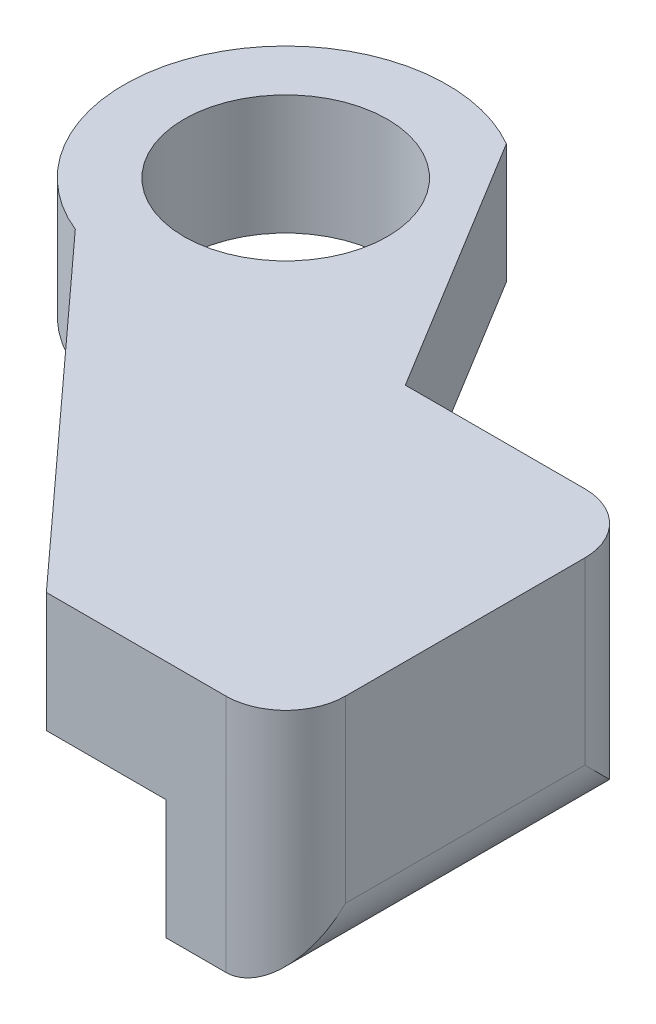
SolidWorks part; units mm, degrees
ref_plane "Front Plane" through (0, 0, 0) normal (0, 0, 1) x (1, 0, 0)
ref_plane "Top Plane" through (0, 0, 0) normal (0, 1, 0) x (1, 0, 0)
ref_plane "Right Plane" through (0, 0, 0) normal (1, 0, 0) x (0, 0, -1)
sketch "Sketch1" plane through (0, 0, 0) normal (0, 1, 0) x (1, 0, 0)
  line L1 (0, 0) -> (20, 0)
  line L2 (0, 0) -> (0, -30)
  line L3 (0, -30) -> (20, -30)
  line L4 (20, 0) -> (20, -30)
  dimension "D1" = 30
  dimension "D2" = 20
extrude "Boss-Extrude1" add sketch "Sketch1" along normal blind 10
sketch "Sketch2" plane through (0, 10, 0) normal (0, 1, 0) x (1, 0, 0)
  line L4 (0, 0) -> (0, -10)
  line L5 (0, -10) -> (10, -10)
  line L6 (10, -10) -> (10, -30)
  line L7 (0, -30) -> (20, -30) construction
  line L8 (10, -30) -> (20, -30)
  line L9 (20, -30) -> (20, 0) construction
  line L10 (20, -30) -> (20, 0)
  line L11 (20, 0) -> (0, 0)
  dimension "D1" = 10
  dimension "D2" = 10
extrude "Boss-Extrude2" add sketch "Sketch2" along normal blind 10
sketch "Sketch4" plane through (0, 10, 0) normal (0, 1, 0) x (1, 0, 0)
  line L0 (0, 0) -> (-13.2471, 21.6896)
  line L1 (0, -30) -> (-25.0721, -2.5109)
  line L2 (0, 0) -> (0, -30)
  line L3 (0, 0) -> (0, -30) construction
  circle A0 centre (-20, 10) radius 8.5
  arc A1 (-13.2471, 21.6896) -> (-25.0721, -2.5109) centre (-20, 10) ccw
  circle A2 centre (-20, 10) radius 13.5 construction
  point P12 (-43.2471, 21.6896)
  point P13 (-55.0721, -2.5109)
  dimension "D1" = 17
  dimension "D3" = 20
  dimension "D4" = 10
  dimension "D2" = 5
extrude "Boss-Extrude3" add sketch "Sketch4" against normal up to surface (10 mm away) up to face at (10, 0, 15)
ref_plane "Plane1" through (0, 5, 0) normal (0, -1, 0) x (-1, 0, 0)
mirror "Mirror1" about plane through (0, 5, 0) normal (0, -1, 0) of "Boss-Extrude2"
sketch "Sketch5" plane through (0, 20, 0) normal (0, 1, 0) x (1, 0, 0)
  line L6 (20, 0) -> (0, 0)
  line L7 (0, 0) -> (0, -10)
  line L8 (0, -10) -> (10, -10)
  line L9 (10, -10) -> (10, -30)
  line L10 (10, -30) -> (20, -30)
  line L11 (20, -30) -> (20, 0)
  line L12 (20, 0) -> (0, 0)
  line L13 (0, 0) -> (0, -10)
  line L14 (0, -10) -> (10, -10)
  line L15 (10, -10) -> (10, -30)
  line L16 (10, -30) -> (20, -30)
  line L17 (20, -30) -> (20, 0)
  dimension "D1" = 0
extrude "Cut-Extrude1" cut sketch "Sketch5" against normal up to surface (10 mm away) up to face at (-4.4699, 10, 7.7834)
fillet "Fillet1" radius 5 4 edges at (0, 0, 5) (20, -10, 15) (20, 0, 0) (20, 0, 30)
